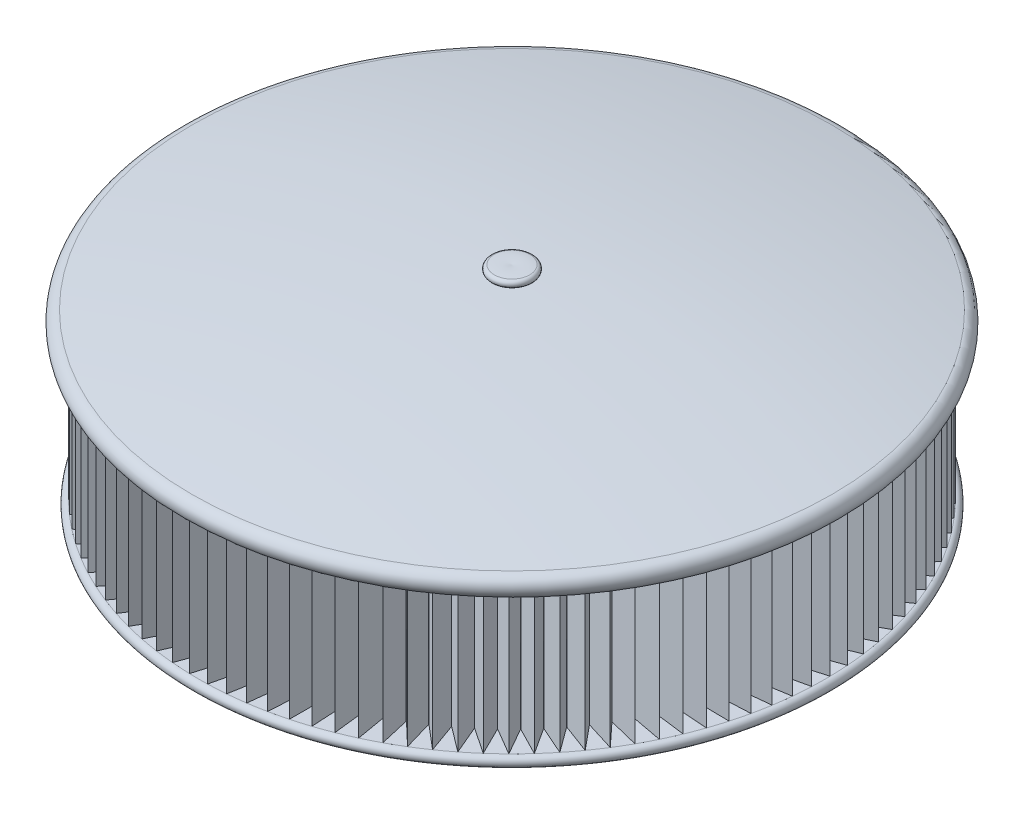
SolidWorks part; units mm, degrees
ref_plane "Front Plane" through (0, 0, 0) normal (0, 0, 1) x (1, 0, 0)
ref_plane "Top Plane" through (0, 0, 0) normal (0, 1, 0) x (1, 0, 0)
ref_plane "Right Plane" through (0, 0, 0) normal (1, 0, 0) x (0, 0, -1)
sketch "Sketch1" plane through (0, 0, 0) normal (0, 1, 0) x (1, 0, 0)
  circle A0 centre (0, 0) radius 55
  circle A1 centre (0, 0) radius 60
  dimension "D1" = 110
  dimension "D2" = 5
extrude "Boss-Extrude1" add sketch "Sketch1" along normal blind 12
sketch "Sketch2" plane through (0, 12, 0) normal (0, 1, 0) x (1, 0, 0)
  circle A0 centre (0, 0) radius 50
  circle A1 centre (0, 0) radius 90
  dimension "D1" = 100
  dimension "D2" = 180
extrude "Boss-Extrude2" add sketch "Sketch2" along normal blind 3
sketch "Sketch3" plane through (0, 15, 0) normal (0, 1, 0) x (1, 0, 0)
  line L0 (0, 0) -> (0, 52.5) construction
  line L1 (41.442, 36.2465) -> (44.5595, 32.3374)
  line L2 (-2.5, 55) -> (2.5, 55)
  line L3 (-2.5, 55) -> (-2.5, 50)
  line L4 (-2.5, 50) -> (2.5, 50)
  line L5 (2.5, 55) -> (2.5, 50)
  line L6 (-2.5, 55) -> (2.5, 50) construction
  line L7 (-2.5, 50) -> (2.5, 55) construction
  line L8 (41.442, 36.2465) -> (37.5328, 33.1291)
  line L9 (37.5328, 33.1291) -> (40.6503, 29.2199)
  line L10 (44.5595, 32.3374) -> (40.6503, 29.2199)
  line L11 (41.442, 36.2465) -> (40.6503, 29.2199) construction
  line L12 (37.5328, 33.1291) -> (44.5595, 32.3374) construction
  line L13 (54.1773, -9.8013) -> (53.0647, -14.676)
  line L14 (54.1773, -9.8013) -> (49.3027, -8.6887)
  line L15 (49.3027, -8.6887) -> (48.1901, -13.5634)
  line L16 (53.0647, -14.676) -> (48.1901, -13.5634)
  line L17 (54.1773, -9.8013) -> (48.1901, -13.5634) construction
  line L18 (49.3027, -8.6887) -> (53.0647, -14.676) construction
  line L19 (26.116, -48.4686) -> (21.6112, -50.638)
  line L20 (26.116, -48.4686) -> (23.9466, -43.9637)
  line L21 (23.9466, -43.9637) -> (19.4418, -46.1332)
  line L22 (21.6112, -50.638) -> (19.4418, -46.1332)
  line L23 (26.116, -48.4686) -> (19.4418, -46.1332) construction
  line L24 (23.9466, -43.9637) -> (21.6112, -50.638) construction
  line L25 (-21.6112, -50.638) -> (-26.116, -48.4686)
  line L26 (-21.6112, -50.638) -> (-19.4418, -46.1332)
  line L27 (-19.4418, -46.1332) -> (-23.9466, -43.9637)
  line L28 (-26.116, -48.4686) -> (-23.9466, -43.9637)
  line L29 (-21.6112, -50.638) -> (-23.9466, -43.9637) construction
  line L30 (-19.4418, -46.1332) -> (-26.116, -48.4686) construction
  line L31 (-53.0647, -14.676) -> (-54.1773, -9.8013)
  line L32 (-53.0647, -14.676) -> (-48.1901, -13.5634)
  line L33 (-48.1901, -13.5634) -> (-49.3027, -8.6887)
  line L34 (-54.1773, -9.8013) -> (-49.3027, -8.6887)
  line L35 (-53.0647, -14.676) -> (-49.3027, -8.6887) construction
  line L36 (-48.1901, -13.5634) -> (-54.1773, -9.8013) construction
  line L37 (-44.5595, 32.3374) -> (-41.442, 36.2465)
  line L38 (-44.5595, 32.3374) -> (-40.6503, 29.2199)
  line L39 (-40.6503, 29.2199) -> (-37.5328, 33.1291)
  line L40 (-41.442, 36.2465) -> (-37.5328, 33.1291)
  line L41 (-44.5595, 32.3374) -> (-37.5328, 33.1291) construction
  line L42 (-40.6503, 29.2199) -> (-41.442, 36.2465) construction
  circle A0 centre (0, 0) radius 50 construction
  point P3 (0, 52.5)
  point P8 (41.0462, 32.7332)
  point P12 (-51.74, -9.245)
  point P17 (51.1837, -11.6823)
  point P22 (22.7789, -47.3009)
  point P27 (-22.7789, -47.3009)
  point P32 (-51.1837, -11.6823)
  point P37 (-41.0462, 32.7332)
  point P42 (0, 0)
  dimension "D1" = 5
  dimension "D2" = 5
  dimension "D4" = 36.9874
  dimension "D3" = 7
extrude "Boss-Extrude3" add sketch "Sketch3" along normal blind 40
sketch "Sketch4" plane through (0, 0, 0) normal (0, 0, 1) x (1, 0, 0)
  line L0 (0, 0) -> (0, 55) construction
  line L1 (-2.5, 55) -> (2.5, 55) construction
  line L2 (0, 55) -> (90, 55)
  line L3 (90.3153, 60.9834) -> (5, 70) construction
  line L4 (5, 70) -> (0, 70) construction
  line L5 (0, 70) -> (0, 55)
  line L6 (5, 70) -> (5, 72) construction
  line L7 (5, 72) -> (0, 72) construction
  line L8 (0, 72) -> (0, 70)
  arc A0 (90, 55) -> (90.3153, 60.9834) centre (90, 58) ccw
  arc A1 (0, 72) -> (5, 72) centre (2.5, 52.1569) cw
  arc A2 (5, 70) -> (5, 72) centre (4.874, 71) ccw
  arc A3 (5, 70) -> (90.3153, 60.9834) centre (-4.6988, -429.9059) cw
  dimension "D2" = 3
  dimension "D6" = 500
  dimension "D7" = 20
  dimension "D1" = 90
  dimension "D3" = 15
  dimension "D4" = 2
  dimension "D5" = 5
revolve "Revolve1" add sketch "Sketch4" angle 360 about L0
fillet "Fillet1" 2 edges at (0, 12, 90) (0, 15, 90) type full round first side face at (0, 12, 60) second side face at (0, 15, 90) middle face at (0, 15, 90)
sketch "Sketch5" plane through (0, 15, 0) normal (0, 1, 0) x (1, 0, 0)
  line L0 (0, 0) -> (0, 88.5) construction
  line L1 (0, 88.5) -> (2.2776, 80)
  line L2 (2.2776, 80) -> (-2.2776, 80)
  line L3 (0, 88.5) -> (-2.2776, 80)
  circle A0 centre (0, 0) radius 88.5 construction
  point P9 (0, 80)
  dimension "D1" = 30
  dimension "D2" = 8.5
extrude "Boss-Extrude4" add sketch "Sketch5" along normal up to next
pattern_circular "CirPattern1" count 109 over 360 about axis through (0, 12, 0) along (0, -1, 0) of "Boss-Extrude4" reverse direction yes
